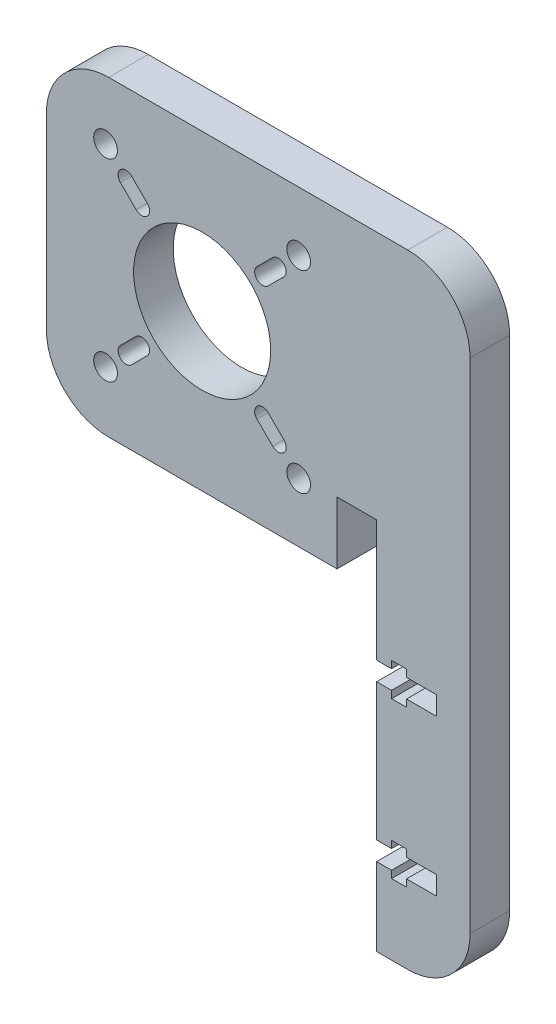
SolidWorks part; units mm, degrees
ref_plane "Front Plane" through (0, 0, 0) normal (0, 0, 1) x (1, 0, 0)
ref_plane "Top Plane" through (0, 0, 0) normal (0, 1, 0) x (1, 0, 0)
ref_plane "Right Plane" through (0, 0, 0) normal (1, 0, 0) x (0, 0, -1)
sketch "Sketch1" plane through (0, 0, 0) normal (0, 0, 1) x (1, 0, 0)
  line L0 (-12.2174, 12.2174) -> (-9.7029, 9.7029) construction
  line L1 (-11.3194, 13.1154) -> (-8.8049, 10.6009)
  line L2 (-13.1154, 11.3194) -> (-10.6009, 8.8049)
  line L3 (-11, 0) -> (11, 0) construction
  line L4 (-9.7029, 9.7029) -> (0, 0) construction
  line L5 (-15.494, 15.494) -> (-10.9972, 10.9972) construction
  line L6 (15.494, 15.494) -> (10.9972, 10.9972) construction
  line L7 (9.7029, 9.7029) -> (0, 0) construction
  line L8 (12.2174, 12.2174) -> (9.7029, 9.7029) construction
  line L9 (13.1154, 11.3194) -> (10.6009, 8.8049)
  line L10 (11.3194, 13.1154) -> (8.8049, 10.6009)
  line L11 (15.494, -15.494) -> (10.9972, -10.9972) construction
  line L12 (9.7029, -9.7029) -> (0, 0) construction
  line L13 (12.2174, -12.2174) -> (9.7029, -9.7029) construction
  line L14 (11.3194, -13.1154) -> (8.8049, -10.6009)
  line L15 (13.1154, -11.3194) -> (10.6009, -8.8049)
  line L16 (-15.494, -15.494) -> (-10.9972, -10.9972) construction
  line L17 (-9.7029, -9.7029) -> (0, 0) construction
  line L18 (-12.2174, -12.2174) -> (-9.7029, -9.7029) construction
  line L19 (-13.1154, -11.3194) -> (-10.6009, -8.8049)
  line L20 (-11.3194, -13.1154) -> (-8.8049, -10.6009)
  line L21 (28, 25) -> (43, 25)
  line L22 (-25, 25) -> (28, 25)
  line L23 (-25, 25) -> (-25, -25)
  line L24 (-25, -25) -> (28, -25)
  line L25 (28, 25) -> (28, -25)
  line L26 (43, 25) -> (43, -75)
  line L27 (43, -75) -> (28, -75)
  line L28 (28, -75) -> (28, -25)
  line L29 (28, -34.5) -> (30.4, -34.5)
  line L30 (30.4, -34.5) -> (30.4, -33.34)
  line L31 (30.4, -33.34) -> (32.8, -33.34)
  line L32 (32.8, -33.34) -> (32.8, -34.5)
  line L33 (32.8, -34.5) -> (37.65, -34.5)
  line L34 (37.65, -34.5) -> (37.65, -37.5)
  line L35 (37.65, -37.5) -> (32.8, -37.5)
  line L36 (32.8, -37.5) -> (32.8, -38.66)
  line L37 (32.8, -38.66) -> (30.4, -38.66)
  line L38 (30.4, -38.66) -> (30.4, -37.5)
  line L39 (30.4, -37.5) -> (28, -37.5)
  line L40 (21.65, -25) -> (21.65, -15)
  line L41 (21.65, -15) -> (28, -15)
  line L42 (28, -59.5) -> (30.4, -59.5)
  line L43 (30.4, -59.5) -> (30.4, -58.34)
  line L44 (30.4, -58.34) -> (32.8, -58.34)
  line L45 (32.8, -58.34) -> (32.8, -59.5)
  line L46 (32.8, -59.5) -> (37.65, -59.5)
  line L47 (37.65, -59.5) -> (37.65, -62.5)
  line L48 (37.65, -62.5) -> (32.8, -62.5)
  line L49 (32.8, -63.66) -> (30.4, -63.66)
  line L50 (32.8, -62.5) -> (32.8, -63.66)
  line L51 (30.4, -63.66) -> (30.4, -62.5)
  line L52 (30.4, -62.5) -> (28, -62.5)
  circle A0 centre (0, 0) radius 11
  arc A1 (-11.3194, 13.1154) -> (-13.1154, 11.3194) centre (-12.2174, 12.2174) ccw
  arc A2 (-10.6009, 8.8049) -> (-8.8049, 10.6009) centre (-9.7029, 9.7029) ccw
  circle A3 centre (-15.494, 15.494) radius 1.905
  circle A4 centre (15.494, 15.494) radius 1.905
  arc A5 (13.1154, 11.3194) -> (11.3194, 13.1154) centre (12.2174, 12.2174) ccw
  arc A6 (8.8049, 10.6009) -> (10.6009, 8.8049) centre (9.7029, 9.7029) ccw
  circle A7 centre (15.494, -15.494) radius 1.905
  arc A8 (11.3194, -13.1154) -> (13.1154, -11.3194) centre (12.2174, -12.2174) ccw
  arc A9 (10.6009, -8.8049) -> (8.8049, -10.6009) centre (9.7029, -9.7029) ccw
  circle A10 centre (-15.494, -15.494) radius 1.905
  arc A11 (-13.1154, -11.3194) -> (-11.3194, -13.1154) centre (-12.2174, -12.2174) ccw
  arc A12 (-8.8049, -10.6009) -> (-10.6009, -8.8049) centre (-9.7029, -9.7029) ccw
  point P5 (-10.9602, 10.9602)
  point P21 (10.9602, 10.9602)
  point P32 (10.9602, -10.9602)
  point P43 (-10.9602, -10.9602)
  point P52 (0, 0)
  point P78 (37.65, -36)
  dimension "D1" = 22
  dimension "D3" = 1.27
  dimension "D6" = 3.81
  dimension "D2" = 1.778
  dimension "D4" = 45
  dimension "D5" = 15.5
  dimension "D7" = 15.494
  dimension "D9" = 25
  dimension "D10" = 50
  dimension "D11" = 25
  dimension "D12" = 53
  dimension "D13" = 3
  dimension "D14" = 9.65
  dimension "D15" = 5.32
  dimension "D16" = 2.4
  dimension "D17" = 2.66
  dimension "D18" = 2.4
  dimension "D19" = 15
  dimension "D20" = 100
  dimension "D21" = 37.5
  dimension "D22" = 6.35
  dimension "D23" = 10
  dimension "D24" = 2
  dimension "D8" = 4
extrude "Boss-Extrude1" add sketch "Sketch1" along normal blind 6.35 contours L25 L22 L23 L24 A12 L20 A11 L19 A10 A9 L15 A8 L14 A7 A6 L10 A5 L9 A4 A3 A2 L2 A1 L1 A0 | L38 L39 L28 L27 L26 L21 L25 L29 L30 L31 L32 L33 L34 L35 L36 L37 | L24 region at (27.2714, 5, 0) region at (35.6386, -23.8663, 0)
fillet "Fillet1" radius 10 4 edges at (43, -75, 3.175) (43, 25, 3.175) (-25, -25, 3.175) (-25, 25, 3.175)
